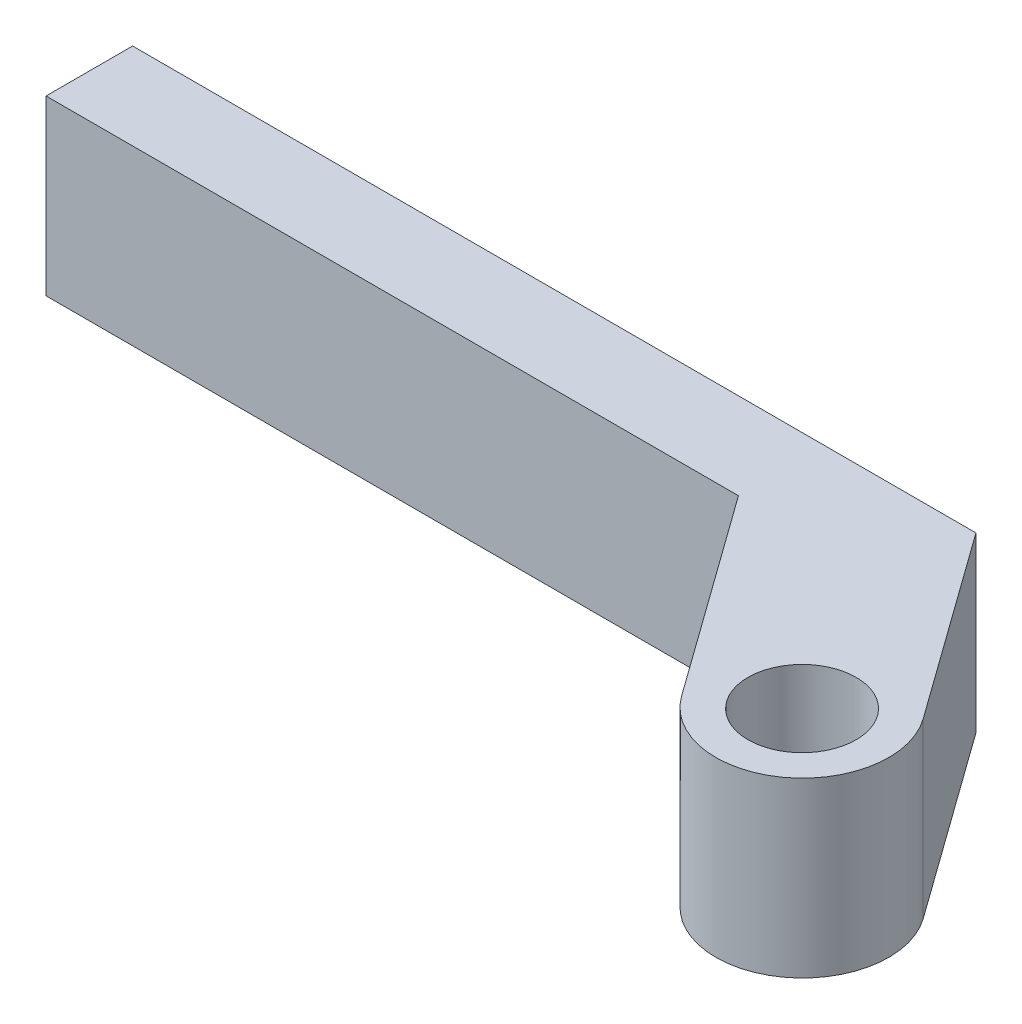
SolidWorks part; units mm, degrees
ref_plane "Front Plane" through (0, 0, 0) normal (0, 0, 1) x (1, 0, 0)
ref_plane "Top Plane" through (0, 0, 0) normal (0, 1, 0) x (1, 0, 0)
ref_plane "Right Plane" through (0, 0, 0) normal (1, 0, 0) x (0, 0, -1)
sketch "Sketch2" plane through (0, 0, 0) normal (0, 1, 0) x (1, 0, 0)
  line L20 (5.1633, -17.7805) -> (-45.4817, -17.7805) construction
  line L21 (-10.6389, -0.318) -> (0.0062, -15.1354)
  line L22 (-61.4389, -0.318) -> (-10.6389, -0.318)
  line L23 (-61.4389, 6.032) -> (-61.4389, -0.318)
  line L24 (-61.4389, 6.032) -> (-10.6389, 6.032)
  line L25 (-10.6389, 6.032) -> (0.4368, 6.032)
  line L26 (10.3205, -7.7255) -> (0.4368, 6.032)
  arc A3 (0.0062, -15.1354) -> (10.3205, -7.7255) centre (5.1633, -11.4305) ccw
extrude "Boss-Extrude1" add sketch "Sketch2" along normal blind 12.7
hole_wizard "3/8-16 Tapped Hole1" positions "Sketch3" profile "Sketch4" tap size "3/8-16" standard "ANSI Inch"
sketch "Sketch3" plane through (0, 12.7, 0) normal (0, 1, 0) x (1, 0, 0)
  line L1 (-10.6389, -0.318) -> (0.0062, -15.1354) construction
  line L2 (5.1633, -17.7805) -> (-27.2831, -17.7805) construction
  arc A1 (0.0062, -15.1354) -> (10.3205, -7.7255) centre (5.1633, -11.4305) ccw construction
  point P0 (5.2187, -11.5076)
  point P20 (8.8683, -16.5876)
  dimension "D1" = 6.35
  dimension "D2" = 5.08
sketch "Sketch4" plane through (5.2187, 12.7, 11.5076) normal (1, 0, 0) x (0, 0, 1)
  line L0 (0, 0) -> (0, 8.7347)
  line L1 (0, 8.7347) -> (3.9687, 6.35)
  line L2 (3.9687, 6.35) -> (3.9688, 0)
  line L5 (3.9688, 0) -> (0, 0)
  line L10 (0, 8.7347) -> (-3.9688, 6.35) construction
  line L11 (0, -6.35) -> (0, 107.95) construction
  dimension "Tap Drill Dia." = 7.9375
  dimension "Tap Drill Depth" = 6.35
  dimension "Drill Angle" = 118
cosmetic thread "Hole Thread1" parameters "D1"=19.05, "D2"=9.525
